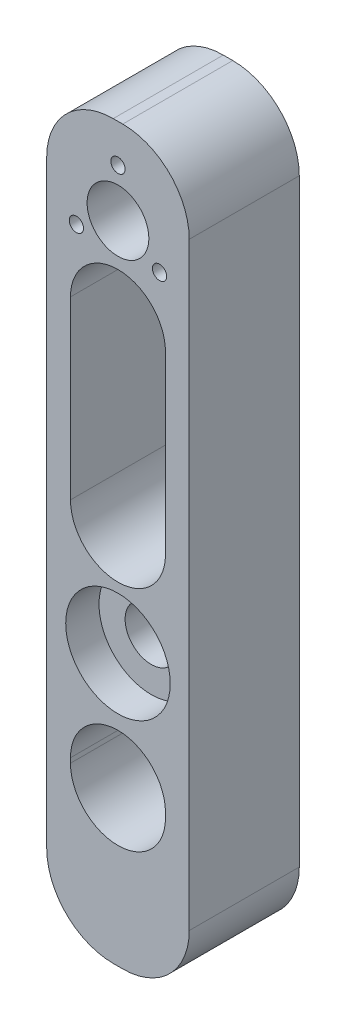
SolidWorks part; units mm, degrees
ref_plane "Front Plane" through (0, 0, 0) normal (0, 0, 1) x (1, 0, 0)
ref_plane "Top Plane" through (0, 0, 0) normal (0, 1, 0) x (1, 0, 0)
ref_plane "Right Plane" through (0, 0, 0) normal (1, 0, 0) x (0, 0, -1)
sketch "Sketch1" plane through (0, 0, 0) normal (0, 0, 1) x (1, 0, 0)
  line L0 (-15, -17) -> (0, 0) construction
  line L1 (-15, 57.0003) -> (15, 57.0003)
  line L2 (-15, 57.0003) -> (-15, -17)
  line L3 (-15, -17) -> (15, -17)
  line L4 (15, 57.0003) -> (15, -17)
  line L5 (0, 0) -> (15, -17) construction
  line L6 (-15, 57.0003) -> (0, 40.0003) construction
  line L7 (0, 40.0003) -> (15, 57.0003) construction
  circle A0 centre (0, 0) radius 7.9823
  circle A1 centre (0, 40.0003) radius 11
  dimension "D3" = 30
  dimension "D4" = 22
  dimension "D5" = 15.9646
  dimension "D1" = 40.0003
  dimension "D2" = 17
extrude "Boss-Extrude1" add sketch "Sketch1" along normal blind 23.1638
sketch "Sketch2" plane through (0, 0, 23.1638) normal (0, 0, 1) x (1, 0, 0)
  circle A0 centre (0, 0) radius 4
  circle A1 centre (0, 0) radius 7.9823 construction
  circle A2 centre (0, 0) radius 7.9823
  dimension "D1" = 8
extrude "Boss-Extrude2" add sketch "Sketch2" against normal up to surface (23.1638 mm away) up to face at (0, 20.0001, 0)
sketch "Sketch3" plane through (0, 0, 23.1638) normal (0, 0, 1) x (1, 0, 0)
  circle A0 centre (0, 0) radius 4
extrude "Boss-Extrude3" add sketch "Sketch3" against normal blind 32.1638
sketch "Sketch4" plane through (0, 0, 0) normal (0, 0, -1) x (-1, 0, 0)
  circle A0 centre (0, 40.0003) radius 11 construction
  circle A1 centre (0, 40.0003) radius 11
  circle A2 centre (0, 40.0003) radius 5.5
  dimension "D1" = 5.5
extrude "Boss-Extrude4" add sketch "Sketch4" against normal blind 16.1638
fillet "Fillet1" radius 14 2 edges at (-15, -17, 11.5819) (15, -17, 11.5819)
sketch "Sketch5" plane through (0, 0, 23.1638) normal (0, 0, 1) x (1, 0, 0)
  line L0 (15, -3) -> (15, 57.0003) construction
  line L1 (-15, 57.0003) -> (15, 57.0003)
  line L2 (-15, 57.0003) -> (-15, 137.0003)
  line L3 (-15, 137.0003) -> (15, 137.0003)
  line L4 (15, 57.0003) -> (15, 137.0003)
  dimension "D1" = 80
extrude "Boss-Extrude5" add sketch "Sketch5" against normal up to surface (23.1638 mm away) up to face at (0, 11.3669, 0)
sketch "Sketch6" plane through (0, 0, 23.1638) normal (0, 0, 1) x (1, 0, 0)
  line L0 (-8.75, 113.8448) -> (8.75, 113.8448) construction
  line L1 (8.75, 113.8448) -> (0, 129.0003) construction
  line L2 (0, 129.0003) -> (-8.75, 113.8448) construction
  line L3 (15, 137.0003) -> (-15, 137.0003) construction
  line L4 (-8.75, 113.8448) -> (0, 118.8966) construction
  line L5 (0, 118.8966) -> (0, 129.0003) construction
  line L6 (8.75, 113.8448) -> (0, 118.8966) construction
  circle A0 centre (-8.75, 113.8448) radius 1.5
  circle A1 centre (8.75, 113.8448) radius 1.5
  circle A2 centre (0, 129.0003) radius 1.5
  circle A3 centre (0, 118.8966) radius 6.5
  point P7 (0, 40.0003)
  dimension "D1" = 3
  dimension "D4" = 13
  dimension "D2" = 8
  dimension "D3" = 17.5
extrude "Cut-Extrude1" cut sketch "Sketch6" against normal through all
sketch "Sketch7" plane through (0, 0, 23.1638) normal (0, 0, 1) x (1, 0, 0)
  line L0 (15, 137.0003) -> (-15, 137.0003) construction
  line L1 (-15, -7) -> (15, -7) construction
  line L2 (-10, 100.0003) -> (-10, 63.0003)
  line L3 (10, 100.0003) -> (10, 63.0003)
  line L4 (-10, 16) -> (-10, 15)
  line L5 (10, 16) -> (10, 15)
  arc A0 (10, 100.0003) -> (-10, 100.0003) centre (0, 100.0003) ccw
  arc A1 (-10, 63.0003) -> (10, 63.0003) centre (0, 63.0003) ccw
  arc A2 (10, 16) -> (-10, 16) centre (0, 16) ccw
  arc A3 (-10, 15) -> (10, 15) centre (0, 15) ccw
  point P1 (0, 0)
  point P3 (0, 40.0003)
  point P5 (10, 16)
  dimension "D1" = 20
  dimension "D2" = 37
  dimension "D3" = 37
  dimension "D4" = 23
  dimension "D5" = 1
extrude "Cut-Extrude2" cut sketch "Sketch7" against normal up to surface (23.1638 mm away) up to face at (-7.25, 113.8448, 0)
fillet "Fillet2" radius 14 2 edges at (15, 137.0003, 11.5819) (-15, 137.0003, 11.5819)
